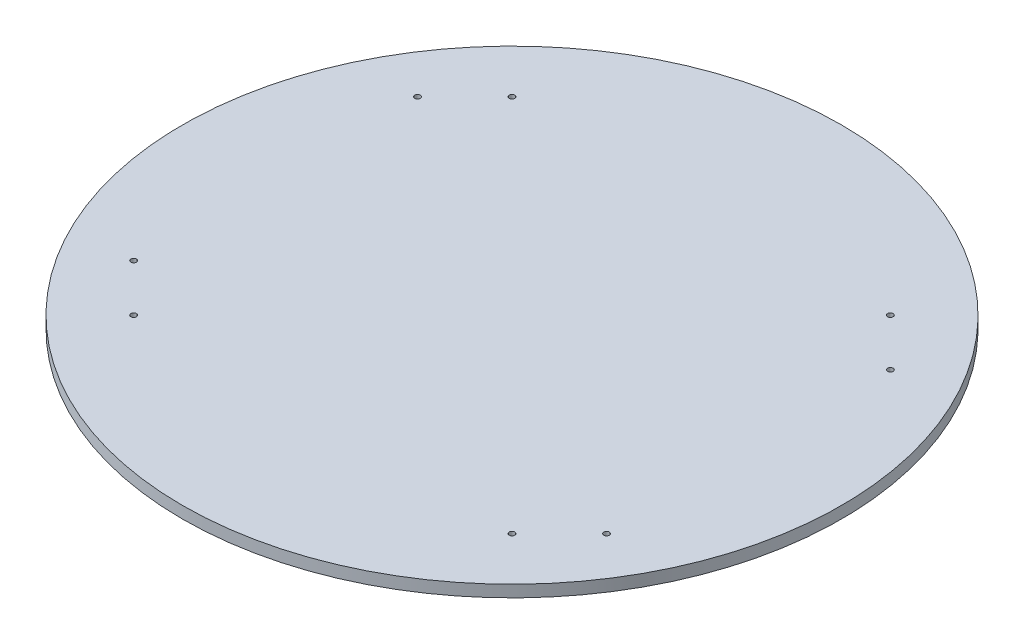
SolidWorks part; units mm, degrees
ref_plane "Front Plane" through (0, 0, 0) normal (0, 0, 1) x (1, 0, 0)
ref_plane "Top Plane" through (0, 0, 0) normal (0, 1, 0) x (1, 0, 0)
ref_plane "Right Plane" through (0, 0, 0) normal (1, 0, 0) x (0, 0, -1)
sketch "Sketch1" plane through (0, 0, 0) normal (0, 1, 0) x (1, 0, 0)
  circle A0 centre (0, 0) radius 177
  circle A1 centre (-101.6, -101.6) radius 1.5
  circle A2 centre (-101.6, 101.6) radius 1.5
  circle A3 centre (101.6, 101.6) radius 1.5
  circle A4 centre (101.6, -101.6) radius 1.5
  circle A5 centre (-127, 76.2) radius 1.5
  circle A6 centre (127, 76.2) radius 1.5
  circle A7 centre (127, -76.2) radius 1.5
  circle A8 centre (-127, -76.2) radius 1.5
  dimension "D1" = 354
  dimension "D2" = 3
  dimension "D3" = 3
  dimension "D4" = 3
  dimension "D5" = 3
  dimension "D8" = 203.2
  dimension "D13" = 3
  dimension "D14" = 3
  dimension "D15" = 3
  dimension "D16" = 3
  dimension "D6" = 203.2
  dimension "D7" = 203.2
  dimension "D9" = 203.2
  dimension "D10" = 0
  dimension "D11" = 101.6
  dimension "D12" = 101.6
  dimension "D17" = 152.4
  dimension "D18" = 152.4
  dimension "D19" = 254
  dimension "D20" = 254
  dimension "D21" = 0
  dimension "D22" = 76.2
  dimension "D23" = 127
extrude "Boss-Extrude1" add sketch "Sketch1" along normal blind 6.35
